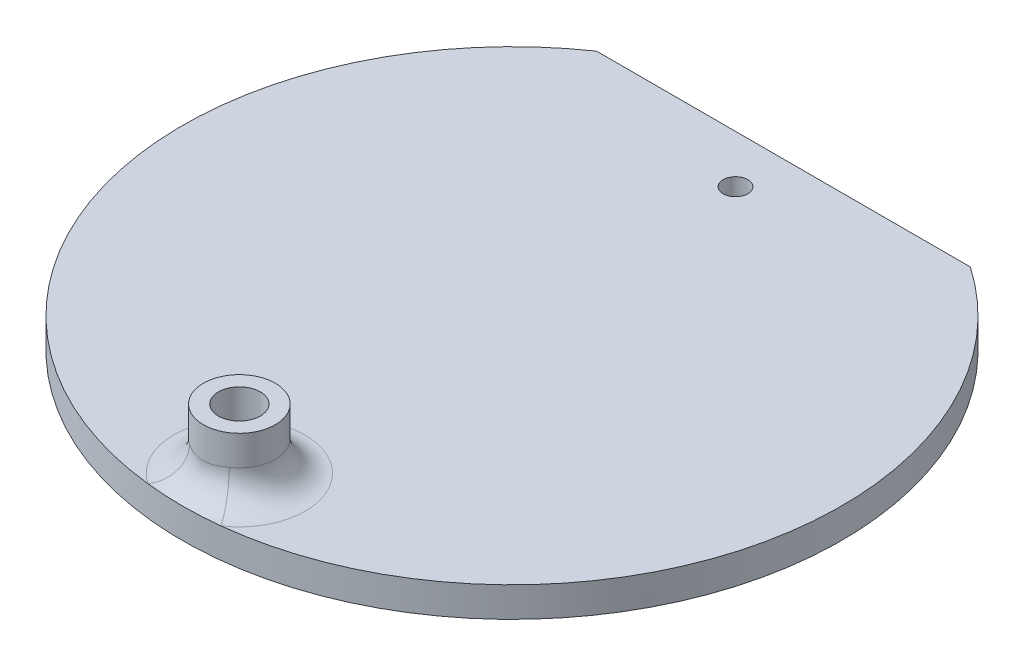
SolidWorks part; units mm, degrees
ref_plane "Front Plane" through (0, 0, 0) normal (0, 0, 1) x (1, 0, 0)
ref_plane "Top Plane" through (0, 0, 0) normal (0, 1, 0) x (1, 0, 0)
ref_plane "Right Plane" through (0, 0, 0) normal (1, 0, 0) x (0, 0, -1)
sketch "Sketch2" plane through (0, 0, 0) normal (0, 1, 0) x (1, 0, 0)
  line L0 (0, 0) -> (0, 63.5) construction
  line L1 (0, 59.055) -> (0, 57.531) construction
  line L2 (0, 57.531) -> (39.6132, 57.531)
  line L3 (0, 57.531) -> (-39.6132, 57.531)
  arc A0 (-39.6132, 57.531) -> (39.6132, 57.531) centre (0, 0) ccw
  circle A1 centre (0, 63.5) radius 4.445 construction
  circle A2 centre (0, 47.371) radius 2.6035
  dimension "D1" = 139.7
  dimension "D3" = 8.89
  dimension "D5" = 5.207
  dimension "D2" = 63.5
  dimension "D4" = 1.524
  dimension "D6" = 10.16
extrude "Boss-Extrude1" add sketch "Sketch2" along normal blind 6.35
sketch "Sketch3" plane through (0, 6.35, 0) normal (0, 1, 0) x (1, 0, 0)
  line L0 (0, 57.531) -> (0, 69.215) construction
  line L1 (39.6132, 57.531) -> (-39.6132, 57.531) construction
  circle A0 centre (0, -57.785) radius 7.62
  dimension "D2" = 15.24
  dimension "D1" = 11.684
  dimension "D3" = 115.316
extrude "Boss-Extrude2" add sketch "Sketch3" along normal blind 12.7 contours A0
sketch "Sketch4" plane through (0, 6.35, 0) normal (0, 1, 0) x (1, 0, 0)
  circle A0 centre (0, -57.785) radius 4.445
  dimension "D1" = 8.89
extrude "Cut-Extrude1" cut sketch "Sketch4" against normal through all both and the other way through all
fillet "Fillet1" radius 6.35 1 edges at (0, 6.35, 65.405)
